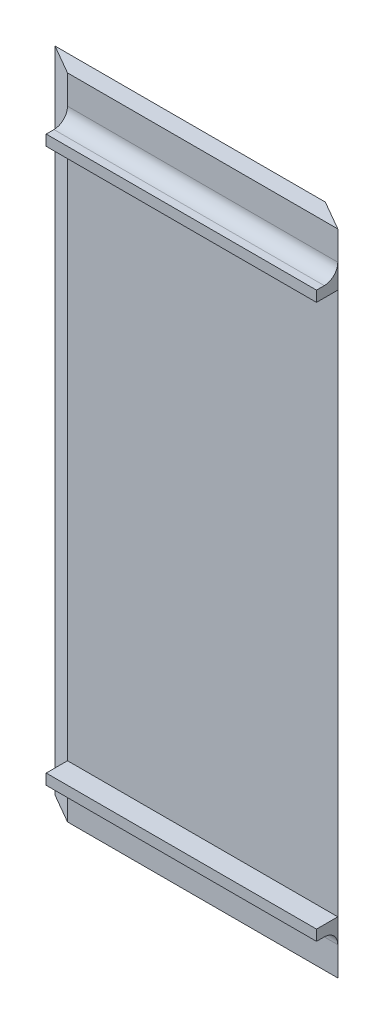
SolidWorks part; units mm, degrees
ref_plane "Front Plane" through (0, 0, 0) normal (0, 0, 1) x (1, 0, 0)
ref_plane "Top Plane" through (0, 0, 0) normal (0, 1, 0) x (1, 0, 0)
ref_plane "Right Plane" through (0, 0, 0) normal (1, 0, 0) x (0, 0, -1)
sketch "Sketch1" plane through (0, 0, 0) normal (0, 0, 1) x (1, 0, 0)
  line L0 (53.7926, 0) -> (53.7926, -121.92)
  line L1 (53.7926, -121.92) -> (2.9926, -121.92)
  line L2 (2.9926, -121.92) -> (2.9926, 0)
  line L3 (2.9926, 0) -> (53.7926, 0)
extrude "Boss-Extrude1" add sketch "Sketch1" against normal blind 3.2
sketch "Sketch2" plane through (0, -121.92, 0) normal (0, -1, 0) x (1, 0, 0)
  line L0 (53.7926, 0) -> (53.7926, -3.2)
  line L1 (53.7926, -3.2) -> (48.2501, -3.2)
  line L2 (2.9926, -3.2) -> (53.7926, -3.2) construction
  line L3 (-56.1926, -63.5) -> (53.7926, 0) construction
  line L4 (48.2501, -3.2) -> (53.7926, 0)
extrude "Cut-Extrude1" cut sketch "Sketch2" against normal through all
sketch "Sketch4" plane through (0, -121.92, 0) normal (0, -1, 0) x (1, 0, 0)
  line L0 (2.9926, 0) -> (2.9926, -3.2)
  line L1 (2.9926, -3.2) -> (-2.5499, -3.2)
  line L3 (-2.5499, -3.2) -> (2.9926, 0)
extrude "Boss-Extrude2" add sketch "Sketch4" against normal up to surface (121.92 mm away) up to face at (27.007, 0, -1.6)
sketch "Sketch5" plane through (0, 0, 0) normal (0, 0, 1) x (1, 0, 0)
  line L0 (53.7926, -9.96) -> (53.7926, -7.96)
  line L1 (53.7926, -121.92) -> (53.7926, 0) construction
  line L2 (53.7926, -7.96) -> (2.9926, -7.96)
  line L3 (2.9926, 0) -> (2.9926, -121.92) construction
  line L4 (2.9926, -7.96) -> (2.9926, -9.96)
  line L5 (2.9926, -9.96) -> (53.7926, -9.96)
  line L6 (-12.7128, -10.46) -> (51.4921, -10.46) construction
  line L7 (53.7926, -60.96) -> (2.9926, -60.96) construction
  line L8 (2.9926, -111.96) -> (53.7926, -111.96)
  line L9 (2.9926, -113.96) -> (2.9926, -111.96)
  line L10 (53.7926, -113.96) -> (2.9926, -113.96)
  line L11 (53.7926, -111.96) -> (53.7926, -113.96)
  dimension "D1" = 2
  dimension "D2" = 0.5
extrude "Boss-Extrude3" add sketch "Sketch5" along normal blind 4
fillet "Fillet1" radius 2.54 2 edges at (28.3926, -7.96, 0) (28.3926, -113.96, 0)
